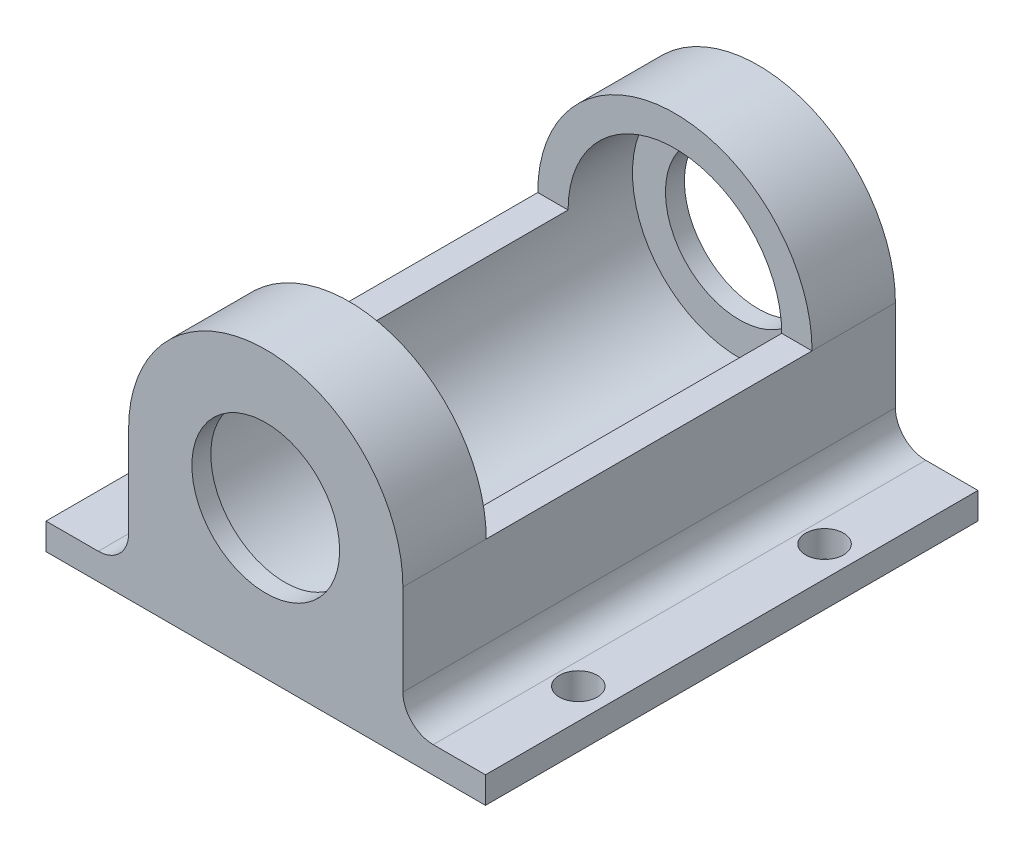
SolidWorks part; units mm, degrees
ref_plane "Front Plane" through (0, 0, 0) normal (0, 0, 1) x (1, 0, 0)
ref_plane "Top Plane" through (0, 0, 0) normal (0, 1, 0) x (1, 0, 0)
ref_plane "Right Plane" through (0, 0, 0) normal (1, 0, 0) x (0, 0, -1)
sketch "Sketch1" plane through (0, 0, 0) normal (0, 1, 0) x (1, 0, 0)
  line L0 (-43.3727, 0) -> (41.7261, 0) construction
  line L1 (-29, -32.5) -> (29, -32.5)
  line L2 (-29, -32.5) -> (-29, 32.5)
  line L3 (-29, 32.5) -> (29, 32.5)
  line L4 (29, -32.5) -> (29, 32.5)
  line L5 (-29, -32.5) -> (29, 32.5) construction
  line L6 (-29, 32.5) -> (29, -32.5) construction
  line L7 (-29, -16.25) -> (29, -16.25) construction
  line L8 (-29, 16.25) -> (29, 16.25) construction
  circle A0 centre (-25, -16.25) radius 2.5
  circle A1 centre (25, -16.25) radius 2.5
  circle A2 centre (25, 16.25) radius 2.5
  circle A3 centre (-25, 16.25) radius 2.5
  point P0 (0, 0)
  point P16 (-25, -16.25)
  point P17 (25, -16.25)
  point P20 (25, 16.25)
  point P23 (-25, 16.25)
  point P24 (0, 0)
  point P25 (0, 0)
  dimension "D3" = 5
  dimension "D5" = 5
  dimension "D11" = 5
  dimension "D12" = 5
  dimension "D1" = 65
  dimension "D2" = 58
  dimension "D4" = 4
  dimension "D6" = 4
  dimension "D7" = 16.25
  dimension "D8" = 16.25
  dimension "D9" = 4
  dimension "D10" = 4
extrude "Boss-Extrude1" add sketch "Sketch1" along normal blind 3.5
sketch "Sketch2" plane through (0, 0, 32.5) normal (0, 0, 1) x (1, 0, 0)
  line L0 (0, -11.0181) -> (0, 49.5169) construction
  line L1 (-29, 3.5) -> (29, 3.5) construction
  line L2 (-41.9601, 19.5) -> (50.3847, 19.5) construction
  line L3 (-18.1, 19.5) -> (-18.1, 3.5)
  line L4 (18.1, 19.5) -> (18.1, 3.5)
  circle A0 centre (0, 19.5) radius 14.1
  circle A1 centre (0, 19.5) radius 9.75
  arc A2 (-18.1, 19.5) -> (18.1, 19.5) centre (0, 19.5) cw
  point P18 (0, 0)
  line M5 (29, 3.5) -> (-29, 3.5)
  dimension "D1" = 28.2
  dimension "D3" = 19.5
  dimension "D6" = 4
  dimension "D2" = 16
extrude "Boss-Extrude2" add sketch "Sketch2" against normal blind 2.5 contours A2 L3 L4 A0 M5 | A0 A1 region at (0, 37.1027, 32.5) region at (-13.7012, 19.5, 32.5)
extrude "Boss-Extrude3" add sketch "Sketch2<3>" against normal blind 11 contours A2 L3 L4 A0 M5 region at (0, 37.1027, 32.5)
sketch "Sketch2<3>" plane through (0, 0, 32.5) normal (0, 0, 1) x (1, 0, 0) same geometry as "Sketch2"
extrude "Boss-Extrude4" add sketch "Sketch2<4>" along normal blind 11 from offset 65 contours A2 L3 L4 A0 M5 region at (0, 37.1027, 32.5) offset against normal yes
sketch "Sketch2<4>" plane through (0, 0, 32.5) normal (0, 0, 1) x (1, 0, 0) same geometry as "Sketch2"
extrude "Boss-Extrude5" add sketch "Sketch2<5>" along normal blind 2.5 from surface contours A0 A1 region at (-13.7012, 19.5, 32.5) starting at face at (0, 8.8875, -32.5)
sketch "Sketch2<5>" plane through (0, 0, 32.5) normal (0, 0, 1) x (1, 0, 0) same geometry as "Sketch2"
fillet "Fillet3" radius 4 4 edges at (-18.1, 3.5, 27) (-18.1, 3.5, -27) (18.1, 3.5, 27) (18.1, 3.5, -27)
sketch "Sketch4" plane through (0, 0, 21.5) normal (0, 0, -1) x (-1, 0, 0)
  line L0 (0, 20.5357) -> (0, 47.1967) construction
  circle A0 centre (0, 35.6) radius 2
  arc A2 (18.1, 19.5) -> (-18.1, 19.5) centre (0, 19.5) ccw construction
  circle A3 centre (0, 19.5) radius 14.1 construction
sketch "Sketch6" plane through (0, 0, -21.5) normal (0, 0, 1) x (1, 0, 0)
  line L0 (-18.1, 7.5) -> (-18.1, 19.5)
  line L1 (-18.1, 19.5) -> (-14.1, 19.5)
  line L2 (14.1, 19.5) -> (18.1, 19.5)
  line L3 (18.1, 7.5) -> (18.1, 19.5)
  line L4 (22.1, 3.5) -> (-22.1, 3.5) construction
  line L5 (-22.1, 3.5) -> (22.1, 3.5)
  circle A0 centre (0, 19.5) radius 14.1 construction
  arc A1 (-14.1, 19.5) -> (14.1, 19.5) centre (0, 19.5) ccw
  arc A2 (-18.1, 7.5) -> (-22.1, 3.5) centre (-22.1, 7.5) cw
  arc A3 (22.1, 3.5) -> (18.1, 7.5) centre (22.1, 7.5) cw
  arc A4 (18.1, 7.5) -> (22.1, 3.5) centre (22.1, 7.5) ccw construction
extrude "Boss-Extrude6" add sketch "Sketch6" along normal through all
